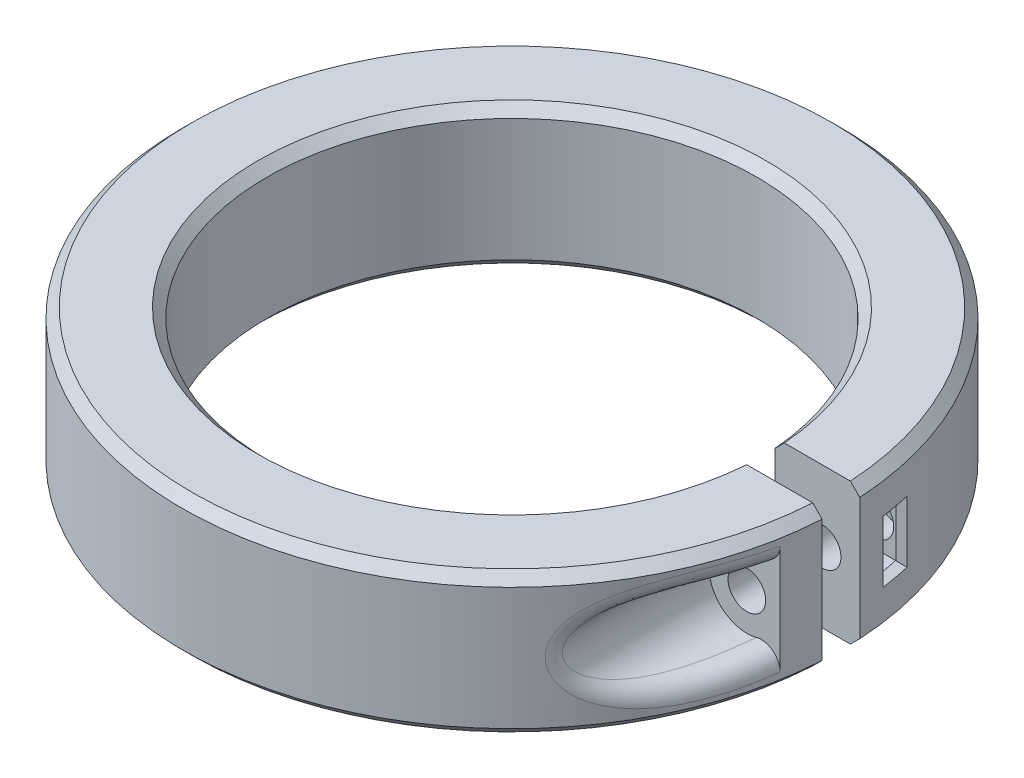
SolidWorks part; units mm, degrees
ref_plane "Front Plane" through (0, 0, 0) normal (0, 0, 1) x (1, 0, 0)
ref_plane "Top Plane" through (0, 0, 0) normal (0, 1, 0) x (1, 0, 0)
ref_plane "Right Plane" through (0, 0, 0) normal (1, 0, 0) x (0, 0, -1)
sketch "Sketch1" plane through (0, 0, 0) normal (0, 1, 0) x (1, 0, 0)
  line L0 (0, 0) -> (35, 0) construction
  line L1 (25.923, -2) -> (34.9428, -2)
  line L2 (25.923, 2) -> (34.9428, 2)
  line L3 (0, 2) -> (35, 2) construction
  line L4 (0, -2) -> (35, -2) construction
  circle A0 centre (0, 0) radius 12.5
  circle A1 centre (0, 0) radius 26
  arc A2 (34.9428, 2) -> (34.9428, -2) centre (0, 0) ccw
  point P5 (0, 0)
  point P7 (34.2649, 0)
  point P8 (35, 0)
  dimension "D1" = 52
  dimension "D2" = 25
  dimension "D3" = 70
  dimension "D4" = 2
  dimension "D5" = 2
extrude "Boss-Extrude1" add sketch "Sketch1" along normal blind 15 contours L2 A2 L1 A1 region at (30.4329, 0, 2.9895)
sketch "Sketch3" plane through (0, 0, -2) normal (0, 0, 1) x (1, 0, 0)
  line L0 (25.923, 15) -> (34.9428, 15) construction
  line L3 (34.9428, 7.5) -> (25.923, 7.5) construction
  line L4 (34.9428, 15) -> (34.9428, 0) construction
  line L5 (25.923, 15) -> (25.923, 0) construction
  line L6 (30.9428, 15) -> (30.9428, 0) construction
  line L7 (25.923, 0) -> (34.9428, 0) construction
  circle A0 centre (30.9428, 7.5) radius 2
  circle A1 centre (30.9428, 7.5) radius 4
  point P0 (30.9428, 15)
  dimension "D2" = 8
  dimension "D3" = 4
  dimension "D1" = 4
extrude "Cut-Extrude1" cut sketch "Sketch3" against normal blind 8 and the other way blind 28 contours A0 region at (30.9428, 7.5, -2)
extrude "Cut-Extrude2" cut sketch "Sketch3<3>" along normal blind 18 from offset 8
sketch "Sketch3<3>" plane through (0, 0, -2) normal (0, 0, 1) x (1, 0, 0) same geometry as "Sketch3"
fillet "Fillet1" radius 2 1 edges at (26.9465, 7.3288, 22.3358)
ref_plane "Plane1" through (35, 0, 0) normal (1, 0, 0) x (0, 0, -1)
sketch "Sketch5" plane through (35, 0, 0) normal (1, 0, 0) x (0, 0, -1)
  line L0 (10, 9.5) -> (2, 9.5) construction
  line L1 (2, 15) -> (2, 0) construction
  line L2 (10, 7.5) -> (2, 7.5) construction
  line L3 (10, 9.5) -> (10, 5.5) construction
  line L4 (2, 9.5) -> (2, 5.5) construction
  line L5 (7.6, 7.5) -> (7.6, 10.5) construction
  line L7 (7.6, 10.5) -> (5, 10.5)
  line L8 (7.6, 10.5) -> (7.6, 4.5)
  line L9 (7.6, 4.5) -> (5, 4.5)
  line L10 (5, 10.5) -> (5, 4.5)
  line L11 (7.6, 10.5) -> (5, 4.5) construction
  line L12 (7.6, 4.5) -> (5, 10.5) construction
  point P0 (5, 9.5)
  point P11 (7.6, 9.5)
  point P17 (6.3, 7.5)
  dimension "D1" = 3
  dimension "D2" = 2.6
  dimension "D3" = 3
  dimension "D4" = 6
extrude "Cut-Extrude3" cut sketch "Sketch5" against normal blind 8
chamfer "Chamfer1" distance 1 angle 15 4 edges at (34.4275, 4.5, -6.3045) (34.641, 7.5, -5) (34.4275, 10.5, -6.3045) (34.1649, 7.5, -7.6) first distance on face at (30.7076, 4.5, -6.3011) first distance on face at (30.9428, 5.5, -5) first distance on face at (30.7076, 10.5, -6.3011) first distance on face at (28.9428, 7.5, -7.6)
chamfer "Chamfer2" distance 1 angle 45 4 edges at (-26, 15, 0) (-26, 0, 0) (-35, 0, 0) (-35, 15, 0)
